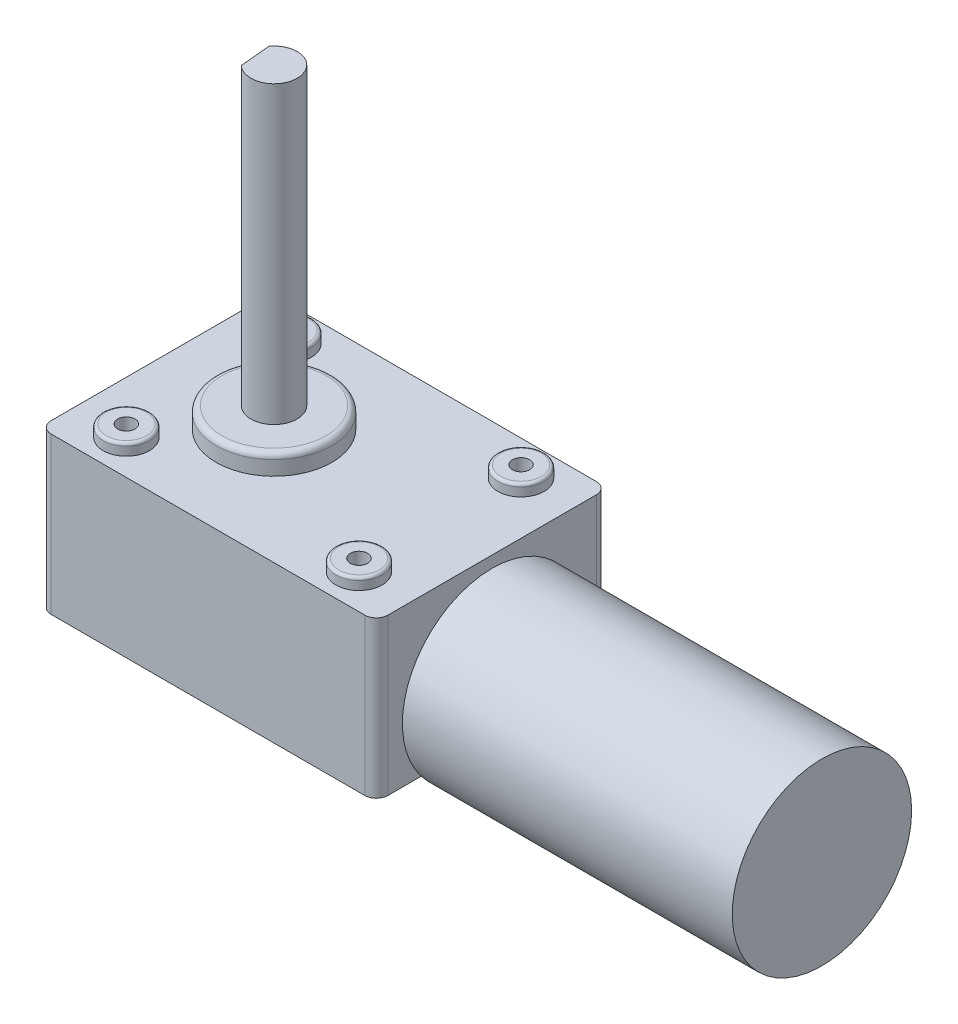
SolidWorks part; units mm, degrees
material "PPS"
ref_plane "Front Plane" through (0, 0, 0) normal (0, 0, 1) x (1, 0, 0)
ref_plane "Top Plane" through (0, 0, 0) normal (0, 1, 0) x (1, 0, 0)
ref_plane "Right Plane" through (0, 0, 0) normal (1, 0, 0) x (0, 0, -1)
sketch "Sketch1" plane through (0, 0, 0) normal (0, 1, 0) x (1, 0, 0)
  line L1 (-66.0502, 26.1223) -> (-7.8502, 26.1223)
  line L2 (-66.0502, 26.1223) -> (-66.0502, -13.8777)
  line L3 (-66.0502, -13.8777) -> (-7.8502, -13.8777)
  line L4 (-7.8502, 26.1223) -> (-7.8502, -13.8777)
  dimension "D1" = 58.2
  dimension "D2" = 40
extrude "Boss-Extrude1" add sketch "Sketch1" along normal blind 27
fillet "Fillet1" radius 2 4 edges at (-7.8502, 13.5, -26.1223) (-66.0502, 13.5, -26.1223) (-66.0502, 13.5, 13.8777) (-7.8502, 13.5, 13.8777)
sketch "Sketch2" plane through (-7.8502, 0, 0) normal (1, 0, 0) x (0, 0, -1)
  line L0 (-11.8777, 27) -> (24.1223, 27) construction
  circle A0 centre (6.1223, 9.5) radius 15.5
  point P4 (6.1223, 27)
  point P5 (6.1223, 25)
  dimension "D1" = 31
  dimension "D2" = 0
  dimension "D3" = 2
extrude "Boss-Extrude2" add sketch "Sketch2" along normal blind 57
sketch "Sketch3" plane through (0, 27, 0) normal (0, 1, 0) x (1, 0, 0)
  line L0 (-66.0502, 24.1223) -> (-66.0502, -11.8777) construction
  line L1 (-7.8502, -11.8777) -> (-7.8502, 24.1223) construction
  line L2 (-64.0502, -13.8777) -> (-9.8502, -13.8777) construction
  line L3 (-9.8502, 26.1223) -> (-64.0502, 26.1223) construction
  circle A0 centre (-16.8502, -7.8777) radius 4
  circle A1 centre (-16.8502, 20.1223) radius 4
  circle A2 centre (-57.0502, -7.8777) radius 4
  circle A3 centre (-57.0502, 20.1223) radius 4
  dimension "D9" = 8
  dimension "D10" = 8
  dimension "D11" = 8
  dimension "D12" = 8
  dimension "D1" = 9
  dimension "D2" = 9
  dimension "D3" = 9
  dimension "D4" = 9
  dimension "D5" = 6
  dimension "D6" = 6
  dimension "D7" = 6
  dimension "D8" = 6
extrude "Boss-Extrude3" add sketch "Sketch3" along normal blind 2
sketch "Sketch4" plane through (0, 27, 0) normal (0, 1, 0) x (1, 0, 0)
  line L0 (-66.0502, 6.1223) -> (-19.9157, 6.1223) construction
  line L1 (-66.0502, 24.1223) -> (-66.0502, -11.8777) construction
  circle A0 centre (-45.53, 6.1223) radius 10
  dimension "D1" = 20
extrude "Boss-Extrude4" add sketch "Sketch4" along normal blind 3.5
ref_plane "Plane1" through (0, 13.5, 0) normal (0, 1, 0) x (1, 0, 0)
mirror "Mirror1" about plane through (0, 13.5, 0) normal (0, 1, 0) of "Boss-Extrude3", "Boss-Extrude4"
fillet "Fillet2" radius 0.5 4 edges at (-57.0502, 29, 11.8777) (-57.0502, 29, -16.1223) (-16.8502, 29, -16.1223) (-16.8502, 29, 11.8777)
fillet "Fillet3" radius 1 1 edges at (-45.53, 30.5, 3.8777)
mirror "Mirror6" about plane through (0, 13.5, 0) normal (0, 1, 0) of "Boss-Extrude3", "Boss-Extrude4"
fillet "Fillet4" radius 0.5 4 edges at (-57.0502, -2, -16.1223) (-57.0502, -2, 11.8777) (-16.8502, -2, 11.8777) (-16.8502, -2, -16.1223)
fillet "Fillet5" radius 1 1 edges at (-45.53, -3.5, 3.8777)
sketch "Sketch5" plane through (0, 30.5, 0) normal (0, 1, 0) x (1, 0, 0)
  line L0 (-48.2704, 3.2086) -> (-48.7634, 8.4771)
  line L1 (-48.5169, 5.8428) -> (-38.4886, 6.7812) construction
  arc A0 (-48.2704, 3.2086) -> (-48.7634, 8.4771) centre (-45.53, 6.1223) ccw
  point P7 (-41.5474, 6.495)
  dimension "D1" = 8
  dimension "D2" = 7
extrude "Boss-Extrude5" add sketch "Sketch5" along normal blind 51
sketch "Sketch6" plane through (0, 29, 0) normal (0, 1, 0) x (1, 0, 0)
  circle A0 centre (-16.8502, -7.8777) radius 1.5
  circle A1 centre (-16.8502, 20.1223) radius 1.5
  circle A2 centre (-57.0502, 20.1223) radius 1.5
  circle A3 centre (-57.0502, -7.8777) radius 1.5
  dimension "D1" = 3
  dimension "D2" = 3
  dimension "D3" = 3
  dimension "D4" = 3
extrude "Cut-Extrude1" cut sketch "Sketch6" against normal blind 10
